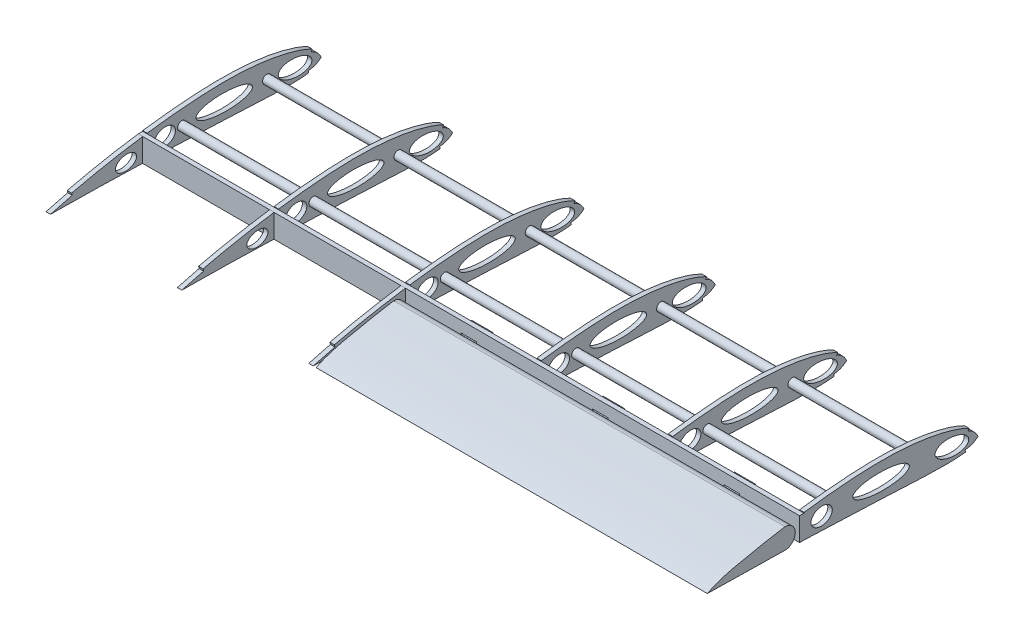
SolidWorks part; units mm, degrees
ref_plane "Front Plane" through (0, 0, 0) normal (0, 0, 1) x (1, 0, 0)
ref_plane "Top Plane" through (0, 0, 0) normal (0, 1, 0) x (1, 0, 0)
ref_plane "Right Plane" through (0, 0, 0) normal (1, 0, 0) x (0, 0, -1)
curve "Curve1"
  spline degree 3 poles (0, 0.2561, 197) (0, 1.149, 193.7201) (0, 2.9304, 187.176) (0, 6.1695, 174.0663) (0, 9.7483, 157.6722) (0, 13.2762, 137.9533) (0, 16.1679, 118.2496) (0, 18.2306, 98.5349) (0, 19.5171, 78.822) (0, 19.5301, 62.3654) (0, 18.621, 49.2257) (0, 17.4237, 39.3576) (0, 15.6579, 29.4682) (0, 13.5343, 21.2733) (0, 11.3895, 14.7062) (0, 9.3648, 9.7544) (0, 7.1751, 5.5294) (0, 4.5558, 1.862) (0, 0.3432, -1.3305) (0, -2.8786, 2.1154) (0, -4.1432, 5.6315) (0, -4.9968, 9.819) (0, -5.4308, 14.7645) (0, -5.7379, 21.3389) (0, -5.7149, 29.5521) (0, -5.4392, 39.4043) (0, -4.9143, 49.2495) (0, -4.3, 62.3829) (0, -3.5118, 78.7969) (0, -2.7716, 98.5006) (0, -1.9498, 118.198) (0, -1.2497, 137.8972) (0, -0.7348, 157.5981) (0, -0.4734, 174.0162) (0, -0.3012, 187.1497) (0, -0.2711, 193.7166) (0, -0.2561, 197) knots 0 0 0 0 0.025305 0.050488 0.10052 0.150191 0.199587 0.24874 0.297716 0.346601 0.371103 0.395726 0.42057 0.445825 0.458702 0.47192 0.485786 0.493461 0.506863 0.516148 0.522766 0.535269 0.547551 0.559786 0.584229 0.608681 0.633151 0.657622 0.706558 0.755482 0.804406 0.85332 0.902221 0.951113 0.975557 1 1 1 1
sketch "Sketch2" plane through (0, 0, 0) normal (1, 0, 0) x (0, 0, -1)
  line L0 (-197, 0.2561) -> (-197, -0.2561)
  line L1 (-197, 0) -> (0, 0) construction
  line L2 (-40, 17.4248) -> (-40, -5.373) construction
  line L3 (-100, 17.9747) -> (-100, -2.6983) construction
  line L4 (0, 0) -> (-40, 6.0259) construction
  line L5 (-40, 6.0259) -> (-100, 7.6382) construction
  line L6 (-100, 7.6382) -> (-197, 0) construction
  line L8 (-124.4398, 15.2116) -> (-124.4398, -1.7354)
  line L11 (-124.4398, 15.2116) -> (-127.6098, 15.2116)
  line L12 (-124.4398, 15.2116) -> (-124.4398, 8.8616)
  line L13 (-124.4398, 8.8616) -> (-127.6098, 8.8616)
  line L14 (-127.6098, 15.2116) -> (-127.6098, 8.8616)
  circle A0 centre (-100, 7.6382) radius 3
  circle A1 centre (-40, 6.0259) radius 3
  ellipse E0 centre (-70, 6.8321) end of major axis (-50.0072, 6.2948) minor radius 6.0022
  ellipse E1 centre (-20, 3.013) end of major axis (-31.8661, 4.8006) minor radius 6
  ellipse E2 centre (-111.963, 6.6962) end of major axis (-104.4861, 7.285) minor radius 6
  ellipse E3 centre (-139.3781, 4.5374) end of major axis (-131.9012, 5.1262) minor radius 5
  spline S0 degree 3 poles (-2505.0904, 6578.1919) (-527.861, -219.0758) (-371.1571, -42.5272) (-174.0663, 6.1695) (-157.6722, 9.7483) (-137.9533, 13.2762) (-118.2496, 16.1679) (-98.5349, 18.2306) (-78.822, 19.5171) (-62.3654, 19.5301) (-49.2257, 18.621) (-39.3576, 17.4237) (-29.4682, 15.6579) (-21.2733, 13.5343) (-14.7062, 11.3895) (-9.7544, 9.3648) (-5.5294, 7.1751) (-1.862, 4.5558) (1.3305, 0.3432) (-2.1154, -2.8786) (-5.6315, -4.1432) (-9.819, -4.9968) (-14.7645, -5.4308) (-21.3389, -5.7379) (-29.5521, -5.7149) (-39.4043, -5.4392) (-49.2495, -4.9143) (-62.3829, -4.3) (-78.7969, -3.5118) (-98.5006, -2.7716) (-118.198, -1.9498) (-137.8972, -1.2497) (-157.5981, -0.7348) (-174.0162, -0.4734) (-446.5443, 3.0993) (-713.3068, -85.3082) (-915.0044, 6909.6127) knots -1.410705 -1.410705 -1.410705 -1.410705 0.025305 0.050488 0.10052 0.150191 0.199587 0.24874 0.297716 0.346601 0.371103 0.395726 0.42057 0.445825 0.458702 0.47192 0.485786 0.493461 0.506863 0.516148 0.522766 0.535269 0.547551 0.559786 0.584229 0.608681 0.633151 0.657622 0.706558 0.755482 0.804406 0.85332 0.902221 0.951113 0.975557 2.931183 2.931183 2.931183 2.931183 only from (-197, 0.2561) to (-197, -0.2561) construction
  spline S1 degree 3 poles (-197, 0.2561) (-193.7201, 1.149) (-187.176, 2.9304) (-174.0663, 6.1695) (-157.6722, 9.7483) (-137.9533, 13.2762) (-118.2496, 16.1679) (-98.5349, 18.2306) (-78.822, 19.5171) (-62.3654, 19.5301) (-49.2257, 18.621) (-39.3576, 17.4237) (-29.4682, 15.6579) (-21.2733, 13.5343) (-14.7062, 11.3895) (-9.7544, 9.3648) (-5.5294, 7.1751) (-1.862, 4.5558) (1.3305, 0.3432) (-2.1154, -2.8786) (-5.6315, -4.1432) (-9.819, -4.9968) (-14.7645, -5.4308) (-21.3389, -5.7379) (-29.5521, -5.7149) (-39.4043, -5.4392) (-49.2495, -4.9143) (-62.3829, -4.3) (-78.7969, -3.5118) (-98.5006, -2.7716) (-118.198, -1.9498) (-137.8972, -1.2497) (-157.5981, -0.7348) (-174.0162, -0.4734) (-187.1497, -0.3012) (-193.7166, -0.2711) (-197, -0.2561) knots 0 0 0 0 0.025305 0.050488 0.10052 0.150191 0.199587 0.24874 0.297716 0.346601 0.371103 0.395726 0.42057 0.445825 0.458702 0.47192 0.485786 0.493461 0.506863 0.516148 0.522766 0.535269 0.547551 0.559786 0.584229 0.608681 0.633151 0.657622 0.706558 0.755482 0.804406 0.85332 0.902221 0.951113 0.975557 1 1 1 1
  dimension "D3" = 6
  dimension "D4" = 6
  dimension "D12" = 5
  dimension "D13" = 3.17
  dimension "D17" = 15
  dimension "D1" = 40
  dimension "D2" = 60
  dimension "D5" = 40
  dimension "D6" = 12
  dimension "D7" = 12
  dimension "D8" = 15
  dimension "D9" = 12
  dimension "D10" = 24
  dimension "D11" = 12
  dimension "D15" = 20
  dimension "D16" = 10
  dimension "D14" = 6.35
extrude "Spars" add sketch "Sketch2" along normal blind 467 contours A1 | A0
extrude "Base Wing" add sketch "Sketch2<9>" along normal blind 3.175 contours A0 | E0 | A1 | E2 | E1 | S1 L0 | E3
sketch "Sketch2<9>" plane through (0, 0, 0) normal (1, 0, 0) x (0, 0, -1) same geometry as "Sketch2"
sketch "Sketch3" plane through (3.175, 0, 0) normal (1, 0, 0) x (0, 0, -1)
  line L0 (-197.1241, 0.224) -> (-177.7605, 5.2292)
  line L1 (-177.7605, 5.2292) -> (-197.1241, 0.224) construction
  line L2 (-177.7605, 5.2292) -> (-177.3632, 3.6922) construction
  line L3 (-197.1241, 0.224) -> (-196.7268, -1.313) construction
  line L4 (-177.3632, 3.6922) -> (-196.7268, -1.313) construction
  line L5 (0, 0) -> (-1.5698, 0.2365) construction
  line L6 (0, 0) -> (-40, 6.0259) construction
  line L7 (-7.8655, 8.3531) -> (-8.591, 6.9411)
  line L8 (-4.3591, 4.3441) -> (-3.3767, 5.5912) construction
  line L9 (-8.591, 6.9411) -> (-4.3591, 4.3441) construction
  line L10 (-4.3591, 4.3441) -> (-1.5698, 0.2365) construction
  line L11 (-5.3287, -3.9604) -> (-5.7651, -2.434) construction
  line L12 (-10.4332, -4.9861) -> (-10.6411, -3.4123)
  line L13 (-3.3767, 5.5912) -> (-2.3943, 6.8382)
  line L14 (-1.5698, 0.2365) -> (-5.7651, -2.434) construction
  line L15 (-10.6411, -3.4123) -> (-5.7651, -2.434) construction
  line L16 (0, 0) -> (1.5698, -0.2365)
  line L17 (-5.3287, -3.9604) -> (-4.8922, -5.4867)
  line L18 (-197.1241, 0.224) -> (-177.7605, 5.2292) construction
  line L23 (-197.1241, 0.224) -> (-197.5214, 1.761) construction
  line L24 (-177.7605, 5.2292) -> (-178.1578, 6.7662) construction
  line L25 (-197.5214, 1.761) -> (-178.1578, 6.7662) construction
  line L26 (-197.5214, 1.761) -> (-196.7268, -1.313)
  line L27 (-197.5214, 1.761) -> (-178.1578, 6.7662)
  line L28 (-196.7268, -1.313) -> (-177.3632, 3.6922)
  line L29 (-178.1578, 6.7662) -> (-177.3632, 3.6922)
  spline S0 degree 3 poles (-197, 0.2561) (-193.7201, 1.149) (-187.176, 2.9304) (-174.0663, 6.1695) (-157.6722, 9.7483) (-137.9533, 13.2762) (-118.2496, 16.1679) (-98.5349, 18.2306) (-78.822, 19.5171) (-62.3654, 19.5301) (-49.2257, 18.621) (-39.3576, 17.4237) (-29.4682, 15.6579) (-21.2733, 13.5343) (-14.7062, 11.3895) (-9.7544, 9.3648) (-5.5294, 7.1751) (-1.862, 4.5558) (1.3305, 0.3432) (-2.1154, -2.8786) (-5.6315, -4.1432) (-9.819, -4.9968) (-14.7645, -5.4308) (-21.3389, -5.7379) (-29.5521, -5.7149) (-39.4043, -5.4392) (-49.2495, -4.9143) (-62.3829, -4.3) (-78.7969, -3.5118) (-98.5006, -2.7716) (-118.198, -1.9498) (-137.8972, -1.2497) (-157.5981, -0.7348) (-174.0162, -0.4734) (-187.1497, -0.3012) (-193.7166, -0.2711) (-197, -0.2561) knots 0 0 0 0 0.025305 0.050488 0.10052 0.150191 0.199587 0.24874 0.297716 0.346601 0.371103 0.395726 0.42057 0.445825 0.458702 0.47192 0.485786 0.493461 0.506863 0.516148 0.522766 0.535269 0.547551 0.559786 0.584229 0.608681 0.633151 0.657622 0.706558 0.755482 0.804406 0.85332 0.902221 0.951113 0.975557 1 1 1 1 construction
  spline S1 degree 2 poles (-8.591, 6.9411) (-3.6378, 5.0995) (-1.5698, 0.2365) knots 0 0 0 1 1 1
  spline S2 degree 2 poles (-10.6411, -3.4123) (-5.4248, -3.2802) (-1.5698, 0.2365) knots 0 0 0 1 1 1
  spline S3 degree 3 poles (-7.8655, 8.3531) (-3.7436, 9.3316) (8.4481, -1.5787) (-6.8965, -7.2435) (-10.4332, -4.9861) knots 0 0 0 0 0.49814 1 1 1 1
  point P5 (-7.8655, 8.3531)
  point P25 (-10.4332, -4.9861)
  point P26 (-5.3287, -3.9604)
  point P27 (0, 0)
  dimension "D6" = 10
  dimension "D4" = 10
  dimension "D1" = 1.5875
  dimension "D2" = 20
  dimension "D3" = 1.5875
  dimension "D5" = 1.5875
pattern_linear "LPattern7" count 3 spacing 92.765 along (1, 0, 0) of "Base Wing"
extrude "Trailing Edge" cut sketch "Sketch3" against normal blind 3.175 contours L27 L29 L28 L26
extrude "Leading Edge" cut sketch "Sketch3<8>" against normal blind 3.175 contours S3 L12 S2 S1 L7
sketch "Sketch3<8>" plane through (3.175, 0, 0) normal (1, 0, 0) x (0, 0, -1) same geometry as "Sketch3"
pattern_linear "LPattern8" count 3 spacing 92.765 along (1, 0, 0) of "Trailing Edge", "Leading Edge"
extrude "Face" cut sketch "Sketch2<10>" along normal blind 3.175 contours L11 L14 L13 L12
sketch "Sketch2<10>" plane through (0, 0, 0) normal (1, 0, 0) x (0, 0, -1) same geometry as "Sketch2"
pattern_linear "LPattern9" count 3 spacing 92.765 along (1, 0, 0) of "Face"
ref_plane "SparPlane" through (0, 0, 127.6098) normal (0, 0, -1) x (-1, 0, 0)
sketch "Sketch12" plane through (0, 0, 127.6098) normal (0, 0, -1) x (-1, 0, 0)
  line L0 (0, 14.7629) -> (0, 8.8616)
  line L1 (0, 8.8616) -> (-3.175, 8.8616)
  line L2 (-3.175, 8.8616) -> (-3.175, -1.7384)
  line L3 (0, 14.7629) -> (-467, 14.7629)
  line L4 (-3.175, -1.7384) -> (-92.765, -1.7384)
  line L5 (-92.765, -1.7384) -> (-92.765, 8.8616)
  line L6 (-92.765, 8.8616) -> (-95.94, 8.8616)
  line L7 (-95.94, 8.8616) -> (-95.94, -1.7384)
  line L8 (-95.94, -1.7384) -> (-185.53, -1.7384)
  line L9 (-185.53, -1.7384) -> (-185.53, 8.8616)
  line L10 (-185.53, 8.8616) -> (-188.705, 8.8616)
  line L11 (-188.705, 8.8616) -> (-188.705, -1.7384)
  line L14 (-188.705, -1.7384) -> (-278.295, -1.7384)
  line L15 (-278.295, -1.7384) -> (-278.295, 8.8616)
  line L16 (-278.295, 8.8616) -> (-281.47, 8.8616)
  line L17 (-281.47, 8.8616) -> (-281.47, -1.7384)
  line L18 (-281.47, -1.7384) -> (-371.06, -1.7384)
  line L19 (-371.06, -1.7384) -> (-371.06, 8.8616)
  line L20 (-371.06, 8.8616) -> (-374.235, 8.8616)
  line L21 (-374.235, 8.8616) -> (-374.235, -1.7384)
  line L23 (-374.235, -1.7384) -> (-463.825, -1.7384)
  line L24 (-463.825, -1.7384) -> (-463.825, 8.8616)
  line L25 (-463.825, 8.8616) -> (-467, 8.8616)
  line L26 (-467, 8.8616) -> (-467, 14.7629)
  line L27 (-463.825, 14.7629) -> (-463.825, 8.8616) construction
  line L28 (-188.705, 14.7629) -> (-188.705, -1.7384) construction
  line L29 (-278.295, 14.7629) -> (-278.295, -1.7384) construction
  line L30 (-281.47, 14.7629) -> (-281.47, -1.7384) construction
  line L31 (-371.06, 14.7629) -> (-371.06, -1.7384) construction
  line L32 (-374.235, 14.7629) -> (-374.235, -1.7384) construction
  line L33 (-188.705, 6.5122) -> (-278.295, 6.5122)
  line L34 (-281.47, 6.5122) -> (-371.06, 6.5122)
  line L35 (-374.235, 6.5122) -> (-463.825, 6.5122)
  line L36 (-228, 6.0122) -> (-228, 7.0122)
  line L37 (-228, 6.0122) -> (-239, 6.0122)
  line L38 (-228, 7.0122) -> (-239, 7.0122)
  line L39 (-239, 6.0122) -> (-239, 7.0122)
  line L40 (-228, 6.0122) -> (-239, 7.0122) construction
  line L41 (-228, 7.0122) -> (-239, 6.0122) construction
  line L46 (-318.765, 4.0122) -> (-318.765, 9.0122)
  line L47 (-318.765, 9.0122) -> (-333.765, 9.0122)
  line L52 (-333.765, 4.0122) -> (-333.765, 9.0122)
  line L53 (-318.765, 4.0122) -> (-333.765, 4.0122)
  line L54 (-226, 4.0122) -> (-226, 9.0122)
  line L55 (-226, 9.0122) -> (-241, 9.0122)
  line L56 (-241, 4.0122) -> (-241, 9.0122)
  line L57 (-226, 4.0122) -> (-241, 4.0122)
  line L58 (-320.765, 6.0122) -> (-320.765, 7.0122)
  line L59 (-320.765, 6.0122) -> (-331.765, 6.0122)
  line L60 (-331.765, 6.0122) -> (-331.765, 7.0122)
  line L61 (-320.765, 7.0122) -> (-331.765, 7.0122)
  line L62 (-320.765, 6.0122) -> (-331.765, 7.0122) construction
  line L63 (-320.765, 7.0122) -> (-331.765, 6.0122) construction
  line L64 (-411.53, 4.0122) -> (-411.53, 9.0122)
  line L65 (-411.53, 9.0122) -> (-426.53, 9.0122)
  line L66 (-426.53, 4.0122) -> (-426.53, 9.0122)
  line L67 (-411.53, 4.0122) -> (-426.53, 4.0122)
  line L68 (-413.53, 6.0122) -> (-413.53, 7.0122)
  line L69 (-413.53, 6.0122) -> (-424.53, 6.0122)
  line L70 (-424.53, 6.0122) -> (-424.53, 7.0122)
  line L71 (-413.53, 7.0122) -> (-424.53, 7.0122)
  line L72 (-413.53, 6.0122) -> (-424.53, 7.0122) construction
  line L73 (-413.53, 7.0122) -> (-424.53, 6.0122) construction
  point P44 (-233.5, 6.5122)
  point P46 (-419.03, 6.5122)
  point P51 (-326.265, 6.5122)
  point P55 (-326.265, 6.5122)
  point P65 (-419.03, 6.5122)
  dimension "D1" = 467
  dimension "D2" = 10.6
  dimension "D3" = 92.765
  dimension "D4" = 11
  dimension "D5" = 1
  dimension "D6" = 2
  dimension "D7" = 3
extrude "Balsa Spar" add sketch "Sketch12" along normal blind 3.175 contours L3 L26 L25 L24 L23 L21 L20 L19 L18 L17 L16 L15 L14 L11 L10 L9 L8 L7 L6 L5 L4 L2 L1 L0
ref_plane "Secondary Plane" through (278.295, 0, 0) normal (1, 0, 0) x (0, 0, -1)
sketch "Sketch13" plane through (278.295, 0, 0) normal (1, 0, 0) x (0, 0, -1)
  line L0 (-127.6098, 8.8616) -> (-124.4398, 8.8616)
  line L1 (-127.6098, 8.8616) -> (-127.6098, -1.7384)
  line L2 (-127.6098, -1.7384) -> (-124.4348, -1.7356)
  line L3 (-124.4398, 8.8616) -> (-124.4398, 14.7629)
  line L4 (-124.4398, 15.2116) -> (-124.4398, 14.7629)
  line L6 (-124.4398, 14.7629) -> (-124.4348, 14.7629)
  line L7 (-124.4348, 14.7629) -> (-124.4348, -1.7356)
  line L11 (-124.4398, 14.7629) -> (-124.4348, 14.7629)
  line L15 (-124.4398, 14.7629) -> (-124.4398, 8.8616)
  line L16 (-124.4398, 15.2116) -> (-124.4398, 14.7629)
  line L17 (-124.4398, 15.2116) -> (-124.4398, 14.7629)
  line L20 (-10.4332, -4.9861) -> (-10.6411, -3.4123)
  line L21 (-10.4332, -4.9861) -> (-10.6411, -3.4123)
  line L22 (-8.591, 6.9411) -> (-7.8655, 8.3531)
  line L23 (-8.591, 6.9411) -> (-7.8655, 8.3531)
  circle A0 centre (-40, 6.0259) radius 3 construction
  circle A1 centre (-40, 6.0259) radius 3
  circle A2 centre (-100, 7.6382) radius 3 construction
  circle A3 centre (-100, 7.6382) radius 3
  ellipse E0 centre (-111.963, 6.6962) end of major axis (-104.4861, 7.285) minor radius 6 construction
  ellipse E1 centre (-70, 6.8321) end of major axis (-50.0072, 6.2948) minor radius 6.0022 construction
  ellipse E2 centre (-20, 3.013) end of major axis (-8.1339, 1.2254) minor radius 6 construction
  ellipse E3 centre (-111.963, 6.6962) end of major axis (-104.4861, 7.285) minor radius 6
  ellipse E4 centre (-70, 6.8321) end of major axis (-50.0072, 6.2948) minor radius 6.0022
  ellipse E5 centre (-20, 3.013) end of major axis (-8.1339, 1.2254) minor radius 6
  parabola Q2 (-10.6411, -3.4123) -> (-1.5698, 0.2365) focus (-8.21, 3.6444) apex (-5.7651, -2.434)
  parabola Q3 (-10.6411, -3.4123) -> (-1.5698, 0.2365) focus (-8.21, 3.6444) apex (-5.7651, -2.434)
  parabola Q4 (-1.5698, 0.2365) -> (-8.591, 6.9411) focus (-8.2542, 0.2651) apex (-4.3591, 4.3441)
  parabola Q5 (-1.5698, 0.2365) -> (-8.591, 6.9411) focus (-8.2542, 0.2651) apex (-4.3591, 4.3441)
  spline S2 degree 3 poles (-1367.7155, -2590.3642) (-923.6568, -46.7157) (-512.7824, 14.5145) (-98.5006, -2.7716) (-78.7969, -3.5118) (-62.3829, -4.3) (-49.2495, -4.9143) (-39.4043, -5.4392) (-29.5521, -5.7149) (-21.3389, -5.7379) (43.0686, -2.729) (98.3082, 46.1829) (278.6729, 2978.1004) knots -2.436694 -2.436694 -2.436694 -2.436694 0.552208 0.601132 0.650055 0.698992 0.723462 0.747933 0.772385 0.796827 0.809062 1.252024 1.252024 1.252024 1.252024 only from (-124.4348, -1.7356) to (-10.4332, -4.9861)
  spline S3 degree 3 poles (-2916.9485, -710.3536) (73.3325, -105.9441) (37.3308, -9.8882) (-14.7062, 11.3895) (-21.2733, 13.5343) (-29.4682, 15.6579) (-39.3576, 17.4237) (-49.2257, 18.621) (-62.3654, 19.5301) (-78.822, 19.5171) (-98.5349, 18.2306) (-428.5049, -16.293) (-710.2974, -378.6878) (-1008.0238, 2779.7932) knots -0.204448 -0.204448 -0.204448 -0.204448 0.1894 0.202617 0.215494 0.240749 0.265593 0.290217 0.314719 0.363604 0.412579 0.461733 2.832769 2.832769 2.832769 2.832769 only from (-7.8655, 8.3531) to (-124.4398, 15.2116)
  spline S4 degree 3 poles (-124.4348, -1.7356) (-122.3565, -1.8115) (-113.7109, -2.137) (-98.5006, -2.7716) (-78.7969, -3.5118) (-62.3829, -4.3) (-49.2495, -4.9143) (-39.4043, -5.4392) (-29.5521, -5.7149) (-21.3389, -5.7379) (-14.96, -5.4399) (-11.8784, -5.177) (-10.4332, -4.9861) knots 0.536725 0.536725 0.536725 0.536725 0.552208 0.601132 0.650055 0.698992 0.723462 0.747933 0.772385 0.796827 0.809062 0.819888 0.819888 0.819888 0.819888
  spline S5 degree 3 poles (-7.8655, 8.3531) (-8.5192, 8.689) (-10.7997, 9.7922) (-14.7062, 11.3895) (-21.2733, 13.5343) (-29.4682, 15.6579) (-39.3576, 17.4237) (-49.2257, 18.621) (-62.3654, 19.5301) (-78.822, 19.5171) (-98.5349, 18.2306) (-113.7356, 16.6402) (-122.3616, 15.4993) (-124.4398, 15.2116) knots 0.183969 0.183969 0.183969 0.183969 0.1894 0.202617 0.215494 0.240749 0.265593 0.290217 0.314719 0.363604 0.412579 0.461733 0.477351 0.477351 0.477351 0.477351
  dimension "D1" = 0
extrude "Secondary Base Wing" add sketch "Sketch13" along normal blind 3.175 contours L3 L0 L1 L2 S4 L21 Q3 Q5 L23 S5 L17 | E4 | E3 | E5 | A1 | A3
pattern_linear "LPattern11" count 3 spacing 92.765 along (1, 0, 0) of "Secondary Base Wing"
ref_plane "Insert Plane" through (0, 0, 124.4348) normal (0, 0, -1) x (-1, 0, 0)
sketch "Sketch15" plane through (0, 0, 124.4348) normal (0, 0, -1) x (-1, 0, 0)
  line L0 (-413.53, 6.0122) -> (-413.53, 7.0122) construction
  line L1 (-413.53, 6.0122) -> (-424.53, 6.0122) construction
  line L2 (-424.53, 6.0122) -> (-424.53, 7.0122) construction
  line L3 (-413.53, 7.0122) -> (-424.53, 7.0122) construction
  line L4 (-426.53, 4.0122) -> (-426.53, 9.0122) construction
  line L5 (-411.53, 4.0122) -> (-426.53, 4.0122) construction
  line L6 (-411.53, 4.0122) -> (-411.53, 9.0122) construction
  line L7 (-411.53, 9.0122) -> (-426.53, 9.0122) construction
  line L8 (-228, 6.0122) -> (-228, 7.0122) construction
  line L9 (-228, 6.0122) -> (-239, 6.0122) construction
  line L10 (-239, 6.0122) -> (-239, 7.0122) construction
  line L11 (-228, 7.0122) -> (-239, 7.0122) construction
  line L12 (-241, 4.0122) -> (-241, 9.0122) construction
  line L13 (-226, 4.0122) -> (-241, 4.0122) construction
  line L14 (-226, 4.0122) -> (-226, 9.0122) construction
  line L15 (-226, 9.0122) -> (-241, 9.0122) construction
  line L16 (-318.765, 4.0122) -> (-318.765, 9.0122) construction
  line L17 (-318.765, 4.0122) -> (-333.765, 4.0122) construction
  line L18 (-333.765, 4.0122) -> (-333.765, 9.0122) construction
  line L19 (-318.765, 9.0122) -> (-333.765, 9.0122) construction
  line L20 (-331.765, 6.0122) -> (-331.765, 7.0122) construction
  line L21 (-320.765, 6.0122) -> (-331.765, 6.0122) construction
  line L22 (-320.765, 7.0122) -> (-331.765, 7.0122) construction
  line L23 (-320.765, 6.0122) -> (-320.765, 7.0122) construction
  line L24 (-413.53, 6.0122) -> (-413.53, 7.0122)
  line L25 (-413.53, 6.0122) -> (-424.53, 6.0122)
  line L26 (-424.53, 6.0122) -> (-424.53, 7.0122)
  line L27 (-413.53, 7.0122) -> (-424.53, 7.0122)
  line L28 (-426.53, 4.0122) -> (-426.53, 9.0122)
  line L29 (-411.53, 4.0122) -> (-426.53, 4.0122)
  line L30 (-411.53, 4.0122) -> (-411.53, 9.0122)
  line L31 (-411.53, 9.0122) -> (-426.53, 9.0122)
  line L32 (-228, 6.0122) -> (-228, 7.0122)
  line L33 (-228, 6.0122) -> (-239, 6.0122)
  line L34 (-239, 6.0122) -> (-239, 7.0122)
  line L35 (-228, 7.0122) -> (-239, 7.0122)
  line L36 (-241, 4.0122) -> (-241, 9.0122)
  line L37 (-226, 4.0122) -> (-241, 4.0122)
  line L38 (-226, 4.0122) -> (-226, 9.0122)
  line L39 (-226, 9.0122) -> (-241, 9.0122)
  line L40 (-318.765, 4.0122) -> (-318.765, 9.0122)
  line L41 (-318.765, 4.0122) -> (-333.765, 4.0122)
  line L42 (-333.765, 4.0122) -> (-333.765, 9.0122)
  line L43 (-318.765, 9.0122) -> (-333.765, 9.0122)
  line L44 (-331.765, 6.0122) -> (-331.765, 7.0122)
  line L45 (-320.765, 6.0122) -> (-331.765, 6.0122)
  line L46 (-320.765, 7.0122) -> (-331.765, 7.0122)
  line L47 (-320.765, 6.0122) -> (-320.765, 7.0122)
extrude "Inserts" add sketch "Sketch15" along normal blind 3.175
pattern_linear "LPattern12" count 2 spacing 3.175 along (0, 0, -1) of "Inserts"
ref_plane "Aileron Plane" through (190.705, 0, 0) normal (1, 0, 0) x (0, 0, -1)
sketch "Sketch17" plane through (190.705, 0, 0) normal (1, 0, 0) x (0, 0, -1)
  line L0 (-137.845, -1.2822) -> (-137.845, 13.1882) construction
  line L1 (-137.845, 5.953) -> (-192.7184, -0.2769) construction
  line L2 (-165.2817, 2.8381) -> (-165.8594, 7.9262) construction
  line L3 (-127.6098, -1.6216) -> (-127.6098, 14.7629)
  line L4 (-177.7605, 5.2292) -> (-177.3632, 3.6922)
  line L5 (-177.3632, 3.6922) -> (-192.7184, -0.2769)
  line L6 (-127.6098, -1.6216) -> (-127.6098, 14.7629)
  line L7 (-177.7605, 5.2292) -> (-177.3632, 3.6922)
  line L8 (-177.3632, 3.6922) -> (-192.7184, -0.2769)
  line L9 (-165.2817, 2.8381) -> (-137.845, 5.953) construction
  line L10 (-165.2817, 2.8381) -> (-137.845, 5.953) construction
  line L11 (-137.845, 5.953) -> (-151.5634, 4.3956) construction
  line L12 (-151.5634, 4.3956) -> (-152.2748, 10.6623) construction
  line L13 (-192.7184, -0.2769) -> (-137.845, -1.2822)
  arc A0 (-137.845, 13.1882) -> (-137.845, -1.2822) centre (-137.845, 5.953) cw
  spline S0 degree 1 poles (-137.845, 13.1882) (-152.2748, 10.6623) knots 0 0 1 1
  spline S1 degree 3 poles (-137.845, 13.1882) (-147.2462, 11.7369) (-165.7323, 8) (-184.2505, 4.0667) (-192.7184, -0.2769) knots 0 0 0 0 0.503218 1 1 1 1
  spline S2 degree 3 poles (-755.0077, 2911.5208) (-583.0658, -47.6094) (-381.5956, 2.2478) (-174.0162, -0.4734) (-157.5981, -0.7348) (284.8785, -12.2997) (716.4734, -159.5093) (1182.3538, 2510.7435) knots -0.630495 -0.630495 -0.630495 -0.630495 0.84159 0.866034 0.914926 0.963827 4.161051 4.161051 4.161051 4.161051 only from (-192.7184, -0.2769) to (-127.6098, -1.6216)
  spline S3 degree 3 poles (793.2444, -2775.7791) (428.7441, -71.8713) (123.9697, 60.136) (-157.6722, 9.7483) (-388.6317, -40.6699) (-579.8547, -228.2766) (82.11, -2940.561) knots -1.9547 -1.9547 -1.9547 -1.9547 0.075147 0.124817 0.17485 1.834535 1.834535 1.834535 1.834535 only from (-127.6098, 14.7629) to (-177.7605, 5.2292)
  spline S4 degree 3 poles (-192.7184, -0.2769) (-190.8622, -0.2868) (-185.7226, -0.3199) (-174.0162, -0.4734) (-157.5981, -0.7348) (-141.035, -1.1677) (-131.0396, -1.5005) (-127.6098, -1.6216) knots 0.827772 0.827772 0.827772 0.827772 0.84159 0.866034 0.914926 0.963827 0.989375 0.989375 0.989375 0.989375
  spline S5 degree 3 poles (-127.6098, 14.7629) (-131.0445, 14.2663) (-141.0695, 12.7187) (-157.6722, 9.7483) (-170.9147, 6.8575) (-177.607, 5.2657) (-177.7605, 5.2292) knots 0.049313 0.049313 0.049313 0.049313 0.075147 0.124817 0.17485 0.176024 0.176024 0.176024 0.176024
  point P8 (-130.6098, 5.953)
  dimension "D2" = 3
  dimension "D1" = 0
extrude "Aileron" add sketch "Sketch17" along normal up to surface (276.295 mm away) separate body contours S1 A0 L13 up to face at (467, 4.1415, 66.7373)
extrude "Holes" cut sketch "Sketch15<3>" along normal blind 3.175 and the other way blind 16 contours L35 L34 L33 L32 | L27 L26 L25 L24 | L46 L44 L45 L47
sketch "Sketch15<3>" plane through (0, 0, 124.4348) normal (0, 0, -1) x (-1, 0, 0) same geometry as "Sketch15"
